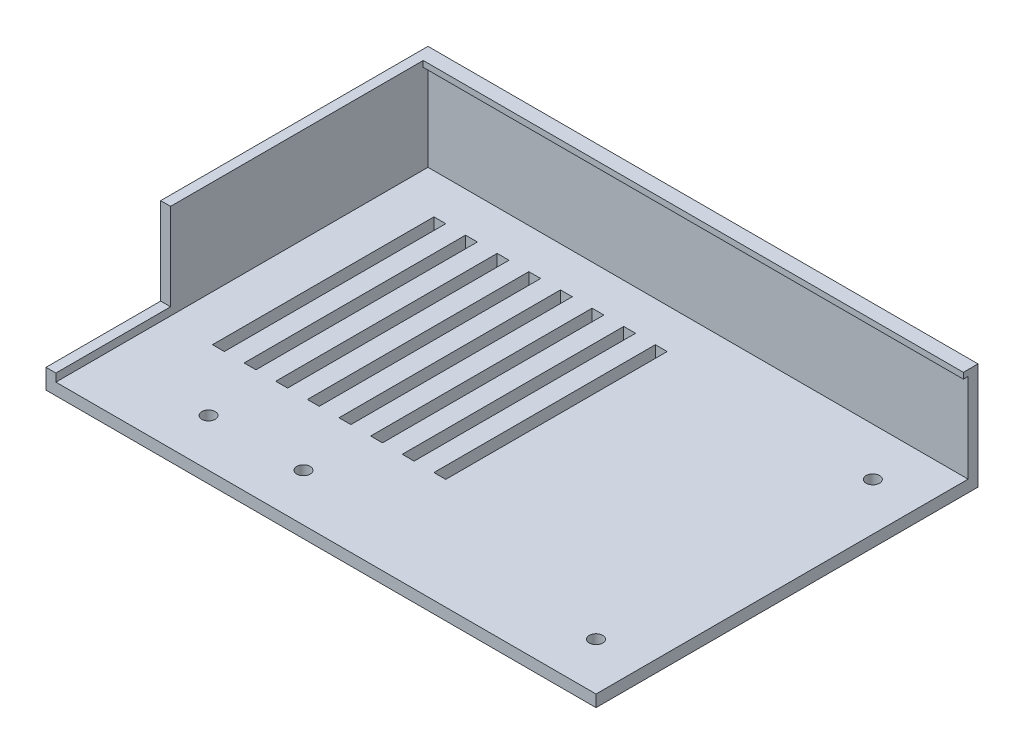
SolidWorks part; units mm, degrees
ref_plane "Front Plane" through (0, 0, 0) normal (0, 0, 1) x (1, 0, 0)
ref_plane "Top Plane" through (0, 0, 0) normal (0, 1, 0) x (1, 0, 0)
ref_plane "Right Plane" through (0, 0, 0) normal (1, 0, 0) x (0, 0, -1)
sketch "Sketch1" plane through (0, 0, 0) normal (0, 1, 0) x (1, 0, 0)
  line L1 (-139.1, -96.6) -> (139.1, -96.6)
  line L2 (-139.1, -96.6) -> (-139.1, 96.6)
  line L3 (-139.1, 96.6) -> (139.1, 96.6)
  line L4 (139.1, -96.6) -> (139.1, 96.6)
  line L5 (-139.1, -96.6) -> (139.1, 96.6) construction
  line L6 (-139.1, 96.6) -> (139.1, -96.6) construction
  point P0 (0, 0)
  dimension "D1" = 278.2
  dimension "D2" = 193.2
extrude "Shell Block" add sketch "Sketch1" along normal blind 27
ref_plane "Shell Front" through (0, 27, 0) normal (0, 1, 0) x (1, 0, 0)
sketch "Sketch2" plane through (0, 27, 0) normal (0, 1, 0) x (1, 0, 0)
  line L1 (-136.6, -92.9) -> (136.6, -92.9)
  line L2 (-136.6, -92.9) -> (-136.6, 92.9)
  line L3 (-136.6, 92.9) -> (136.6, 92.9)
  line L4 (136.6, -92.9) -> (136.6, 92.9)
  line L5 (-136.6, -92.9) -> (136.6, 92.9) construction
  line L6 (-136.6, 92.9) -> (136.6, -92.9) construction
  point P0 (0, 0)
  dimension "D1" = 273.2
  dimension "D2" = 185.8
extrude "Front Opening" cut sketch "Sketch2" against normal blind 1.5
ref_plane "Under Lip" through (0, 25.5, 0) normal (0, 1, 0) x (1, 0, 0)
sketch "Sketch3" plane through (0, 25.5, 0) normal (0, 1, 0) x (1, 0, 0)
  line L1 (-136.6, -94.1) -> (136.6, -94.1)
  line L2 (-136.6, -94.1) -> (-136.6, 94.1)
  line L3 (-136.6, 94.1) -> (136.6, 94.1)
  line L4 (136.6, -94.1) -> (136.6, 94.1)
  line L5 (-136.6, -94.1) -> (136.6, 94.1) construction
  line L6 (-136.6, 94.1) -> (136.6, -94.1) construction
  point P0 (0, 0)
  dimension "D1" = 273.2
  dimension "D2" = 188.2
extrude "Display Pocket" cut sketch "Sketch3" against normal blind 22.5
ref_plane "Back Inner" through (0, 3, 0) normal (0, 1, 0) x (1, 0, 0)
sketch "Sketch4" plane through (0, 3, 0) normal (0, 1, 0) x (1, 0, 0)
  line L1 (-69, 28) -> (-66, 28)
  line L2 (-69, 28) -> (-69, 84)
  line L3 (-69, 84) -> (-66, 84)
  line L4 (-66, 28) -> (-66, 84)
  line L6 (-69, -84) -> (-66, -84)
  line L7 (-69, -84) -> (-69, -28)
  line L8 (-69, -28) -> (-66, -28)
  line L9 (-66, -84) -> (-66, -28)
  line L11 (-77, 28) -> (-74, 28)
  line L12 (-77, 28) -> (-77, 84)
  line L13 (-77, 84) -> (-74, 84)
  line L14 (-74, 28) -> (-74, 84)
  line L16 (-77, -84) -> (-74, -84)
  line L17 (-77, -84) -> (-77, -28)
  line L18 (-77, -28) -> (-74, -28)
  line L19 (-74, -84) -> (-74, -28)
  line L21 (-85, 28) -> (-82, 28)
  line L22 (-85, 28) -> (-85, 84)
  line L23 (-85, 84) -> (-82, 84)
  line L24 (-82, 28) -> (-82, 84)
  line L26 (-85, -84) -> (-82, -84)
  line L27 (-85, -84) -> (-85, -28)
  line L28 (-85, -28) -> (-82, -28)
  line L29 (-82, -84) -> (-82, -28)
  line L31 (-93, 28) -> (-90, 28)
  line L32 (-93, 28) -> (-93, 84)
  line L33 (-93, 84) -> (-90, 84)
  line L34 (-90, 28) -> (-90, 84)
  line L36 (-93, -84) -> (-90, -84)
  line L37 (-93, -84) -> (-93, -28)
  line L38 (-93, -28) -> (-90, -28)
  line L39 (-90, -84) -> (-90, -28)
  line L41 (-101, 28) -> (-98, 28)
  line L42 (-101, 28) -> (-101, 84)
  line L43 (-101, 84) -> (-98, 84)
  line L44 (-98, 28) -> (-98, 84)
  line L46 (-101, -84) -> (-98, -84)
  line L47 (-101, -84) -> (-101, -28)
  line L48 (-101, -28) -> (-98, -28)
  line L49 (-98, -84) -> (-98, -28)
  line L51 (-109, 28) -> (-106, 28)
  line L52 (-109, 28) -> (-109, 84)
  line L53 (-109, 84) -> (-106, 84)
  line L54 (-106, 28) -> (-106, 84)
  line L56 (-109, -84) -> (-106, -84)
  line L57 (-109, -84) -> (-109, -28)
  line L58 (-109, -28) -> (-106, -28)
  line L59 (-106, -84) -> (-106, -28)
  line L61 (-117, 28) -> (-114, 28)
  line L62 (-117, 28) -> (-117, 84)
  line L63 (-117, 84) -> (-114, 84)
  line L64 (-114, 28) -> (-114, 84)
  line L66 (-117, -84) -> (-114, -84)
  line L67 (-117, -84) -> (-117, -28)
  line L68 (-117, -28) -> (-114, -28)
  line L69 (-114, -84) -> (-114, -28)
  line L71 (-125, 28) -> (-122, 28)
  line L72 (-125, 28) -> (-125, 84)
  line L73 (-125, 84) -> (-122, 84)
  line L74 (-122, 28) -> (-122, 84)
  line L76 (-125, -84) -> (-122, -84)
  line L77 (-125, -84) -> (-125, -28)
  line L78 (-125, -28) -> (-122, -28)
  line L79 (-122, -84) -> (-122, -28)
extrude "Vent Slots" cut sketch "Sketch4" against normal blind 4
sketch "Sketch5" plane through (0, 0, 0) normal (1, 0, 0) x (0, 0, -1)
  line L1 (-29, 5) -> (29, 5)
  line L2 (-29, 5) -> (-29, 28)
  line L3 (-29, 28) -> (29, 28)
  line L4 (29, 5) -> (29, 28)
extrude "Cable Exit (-X short side)" cut sketch "Sketch5" against normal blind 140.1
sketch "Sketch6" plane through (0, 3, 0) normal (0, 1, 0) x (1, 0, 0)
  circle A0 centre (-40, -29) radius 1.7
  circle A1 centre (-40, -89) radius 1.7
  circle A2 centre (40, -29) radius 1.7
  circle A3 centre (40, -89) radius 1.7
  circle A4 centre (-52, -47) radius 1.7
  circle A5 centre (-52, -71) radius 1.7
  circle A6 centre (52, -47) radius 1.7
  circle A7 centre (52, -71) radius 1.7
  circle A8 centre (-12, 82) radius 1.7
  circle A9 centre (12, 82) radius 1.7
  circle A10 centre (124, 12) radius 1.7
  circle A11 centre (124, -12) radius 1.7
  circle A12 centre (-12, 12) radius 1.7
  circle A13 centre (-12, -12) radius 1.7
  circle A14 centre (12, 12) radius 1.7
  circle A15 centre (12, -12) radius 1.7
  circle A16 centre (-110, -12) radius 1.7
  circle A17 centre (-110, 12) radius 1.7
  circle A18 centre (-86, -12) radius 1.7
  circle A19 centre (-86, 12) radius 1.7
extrude "Bolt Holes" cut sketch "Sketch6" against normal blind 4
sketch "Sketch7" plane through (0, 0, 0) normal (0, 1, 0) x (1, 0, 0)
  line L1 (200, -200) -> (0, -200)
  line L2 (200, -200) -> (200, 200)
  line L3 (200, 200) -> (0, 200)
  line L4 (0, -200) -> (0, 200)
extrude "Keep one half (X)" cut sketch "Sketch7" against normal through all and the other way through all
sketch "Sketch8" plane through (0, 0, 0) normal (0, 1, 0) x (1, 0, 0)
  line L1 (-200, 0) -> (200, 0)
  line L2 (-200, 0) -> (-200, -200)
  line L3 (-200, -200) -> (200, -200)
  line L4 (200, 0) -> (200, -200)
extrude "Keep one quarter (Z)" cut sketch "Sketch8" against normal through all and the other way through all
equation "\"DispL\"= 272.0"
equation "\"DispW\"= 187.0"
equation "\"DispT\"= 20.0"
equation "\"Clr\"= 0.6"
equation "\"Wall\"= 2.5"
equation "\"BackT\"= 3.0"
equation "\"CableRoom\"= 4.0"
equation "\"LipW\"= 1.2"
equation "\"LipT\"= 1.5"
equation "\"CableW\"= 58.0"
equation "\"CableH\"= 16.0"
equation "\"BoltD\"= 3.4"
equation "\"ShellL\"= \"DispL\" + 2 * \"Clr\" + 2 * \"Wall\""
equation "\"ShellW\"= \"DispW\" + 2 * \"Clr\" + 2 * \"Wall\""
equation "\"ShellH\"= \"BackT\" + \"DispT\" + \"CableRoom\""
equation "\"D1@Sketch1\" = \"ShellL\""
equation "\"D2@Sketch1\" = \"ShellW\""
equation "\"D1@Shell Block\" = \"ShellH\""
equation "\"D1@Shell Front\" = \"ShellH\""
equation "\"D1@Sketch2\" = \"DispL\" + 2 * \"Clr\""
equation "\"D2@Sketch2\" = \"DispW\" + 2 * \"Clr\" - 2 * \"LipW\""
equation "\"D1@Front Opening\" = \"LipT\""
equation "\"D1@Under Lip\" = \"ShellH\" - \"LipT\""
equation "\"D1@Sketch3\" = \"DispL\" + 2 * \"Clr\""
equation "\"D2@Sketch3\" = \"DispW\" + 2 * \"Clr\""
equation "\"D1@Display Pocket\" = \"ShellH\" - \"LipT\" - \"BackT\""
equation "\"D1@Back Inner\" = \"BackT\""
